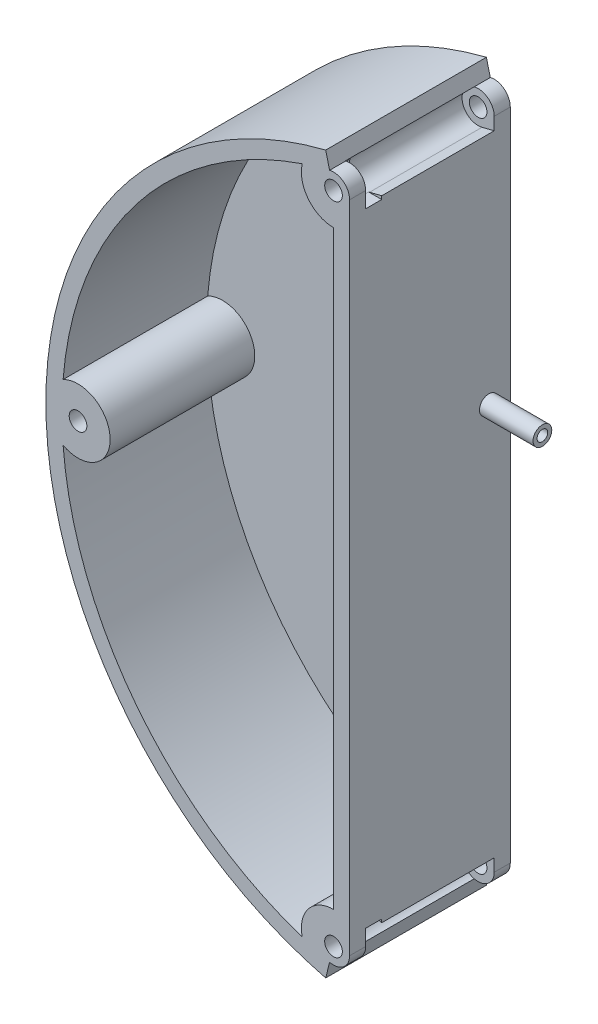
SolidWorks part; units mm, degrees
ref_plane "Front Plane" through (0, 0, 0) normal (0, 0, 1) x (1, 0, 0)
ref_plane "Top Plane" through (0, 0, 0) normal (0, 1, 0) x (1, 0, 0)
ref_plane "Right Plane" through (0, 0, 0) normal (1, 0, 0) x (0, 0, -1)
sketch "Sketch1" plane through (0, 0, 0) normal (0, 0, 1) x (1, 0, 0)
  line L0 (-12.3, -61.1139) -> (-12.3, 61.1139)
  line L1 (-12, -28.4) -> (-12, -52) construction
  line L2 (-16.7571, 66.9343) -> (-16.0286, 64.0241)
  line L4 (-16.7571, -66.9343) -> (-16.0286, -64.0241)
  line L5 (-63, 0) -> (0, 0) construction
  arc A1 (-16.0286, -64.0241) -> (-12.3, -61.1139) centre (-15.3, -61.1139) cw
  arc A3 (-16.0286, 64.0241) -> (-12.3, 61.1139) centre (-15.3, 61.1139) ccw
  circle A4 centre (-63, 0) radius 3
  arc A6 (-16.7571, 66.9343) -> (-16.7571, -66.9343) centre (0, 0) ccw
  dimension "D2" = 3
  dimension "D6" = 3
  dimension "D7" = 14.055
  dimension "D8" = 6
  dimension "D4" = 69
  dimension "D1" = 0.3
  dimension "D3" = 3
  dimension "D5" = 3
  dimension "D9" = 63
  dimension "D10" = 14.055
extrude "Boss-Extrude2" add sketch "Sketch1" along normal blind 30
shell "Shell1" thickness 3 removed face at (-24.7296, 0, 30)
sketch "Sketch3" plane through (-12.3, 0, 0) normal (1, 0, 0) x (0, 1, 0)
  line L0 (-61.1139, 0) -> (61.1139, 0) construction
  circle A0 centre (15, 4) radius 1.75
  dimension "D1" = 3.5
  dimension "D2" = 4
  dimension "D3" = 15
extrude "Boss-Extrude3" add sketch "Sketch3" along normal blind 10
sketch "Sketch5" plane through (0, 0, 0) normal (0, 0, 1) x (1, 0, 0)
  line L0 (-12.3, -61.1139) -> (-12.3, 61.1139)
  line L2 (-16.7571, 66.9343) -> (-16.0286, 64.0241)
  line L4 (-16.7571, -66.9343) -> (-16.0286, -64.0241)
  line L5 (-63, 0) -> (0, 0) construction
  circle A4 centre (-63, 0) radius 1.65
  circle A5 centre (-15.3, 61.1139) radius 1.65
  arc A6 (-16.7571, 66.9343) -> (-16.7571, -66.9343) centre (0, 0) ccw
  arc A7 (-16.0286, 64.0241) -> (-12.3, 61.1139) centre (-15.3, 61.1139) cw
  circle A8 centre (-15.3, -61.1139) radius 1.65
  arc A9 (-12.3, -61.1139) -> (-16.0286, -64.0241) centre (-15.3, -61.1139) cw
  dimension "D2" = 3.3
  dimension "D8" = 3.3
  dimension "D1" = 3.3
  dimension "D3" = 3
  dimension "D5" = 3
extrude "Boss-Extrude4" add sketch "Sketch5" along normal blind 3 contours A4 L0 A7 L2 A6 L4 A9 A8 A5 region at (-36.1775, 0, 0)
sketch "Sketch6" plane through (0, 0, 30) normal (0, 0, 1) x (1, 0, 0)
  line L0 (-63, 3) -> (-68.9348, 3)
  line L1 (-63, -3) -> (-68.9348, -3)
  line L2 (-16.0286, -64.0241) -> (-14.5714, -58.2037) construction
  line L3 (-14.5714, -58.2037) -> (-12.3, -58.7724)
  line L4 (-12.3, -61.1139) -> (-12.3, 61.1139) construction
  line L5 (-12.3, -58.7724) -> (-12.3, -61.1139)
  line L6 (-16.0286, 64.0241) -> (-14.5714, 58.2037) construction
  line L7 (-14.5714, 58.2037) -> (-12.3, 58.7724)
  line L8 (-12.3, 58.7724) -> (-12.3, 61.1139)
  arc A1 (-63, -3) -> (-63, 3) centre (-63, 0) ccw
  arc A2 (-12.3, -61.1139) -> (-14.5714, -58.2037) centre (-15.3, -61.1139) ccw
  arc A3 (-14.5714, 58.2037) -> (-12.3, 61.1139) centre (-15.3, 61.1139) ccw
  arc A4 (-16.7571, 66.9343) -> (-16.7571, -66.9343) centre (0, 0) ccw construction
  arc A5 (-68.9348, 3) -> (-68.9348, -3) centre (-68.9348, 0) ccw
  arc A6 (-12.3, -61.1139) -> (-16.0286, -64.0241) centre (-15.3, -61.1139) ccw construction
  arc A7 (-16.0286, 64.0241) -> (-12.3, 61.1139) centre (-15.3, 61.1139) ccw construction
extrude "Cut-Extrude1" cut sketch "Sketch6" against normal up to surface (27 mm away) up to face at (-61.35, 0, 3)
sketch "Sketch7" plane through (0, 0, 30) normal (0, 0, 1) x (1, 0, 0)
  line L0 (-13.5968, -58.1639) -> (-11.8936, -58.1639)
  line L1 (-11.8936, -61.1139) -> (-13.5968, -58.1639) construction
  line L2 (-13.5968, -58.1639) -> (-17.0032, -58.1639)
  line L3 (-17.0032, -58.1639) -> (-18.7064, -61.1139)
  line L4 (-18.7064, -61.1139) -> (-17.0032, -64.0639)
  line L5 (-17.0032, -64.0639) -> (-13.5968, -64.0639)
  line L6 (-13.5968, -64.0639) -> (-11.8936, -61.1139)
  line L7 (-11.8936, 61.1139) -> (-13.5968, 64.0639)
  line L8 (-13.5968, 64.0639) -> (-17.0032, 64.0639)
  line L9 (-17.0032, 64.0639) -> (-18.7064, 61.1139)
  line L10 (-18.7064, 61.1139) -> (-17.0032, 58.1639)
  line L11 (-17.0032, 58.1639) -> (-13.5968, 58.1639)
  line L12 (-13.5968, 58.1639) -> (-11.8936, 61.1139) construction
  line L13 (-59.5936, 0) -> (-61.2968, 2.95)
  line L14 (-61.2968, 2.95) -> (-64.7032, 2.95)
  line L15 (-64.7032, 2.95) -> (-66.4064, 0)
  line L16 (-66.4064, 0) -> (-64.7032, -2.95)
  line L17 (-64.7032, -2.95) -> (-61.2968, -2.95)
  line L18 (-61.2968, -2.95) -> (-59.5936, 0)
  line L19 (-11.8936, -58.1639) -> (-11.8936, -61.1139)
  line L20 (-13.5968, 58.1639) -> (-11.8936, 58.1639)
  line L21 (-11.8936, 58.1639) -> (-11.8936, 61.1139)
  circle A0 centre (-15.3, -61.1139) radius 2.95 construction
  circle A1 centre (-15.3, 61.1139) radius 2.95 construction
  circle A2 centre (-63, 0) radius 2.95 construction
  dimension "D1" = 5.9
  dimension "D2" = 5.9
  dimension "D3" = 5.9
extrude "Cut-Extrude2" cut sketch "Sketch7" against normal blind 3 from offset 3 offset against normal yes
sketch "Sketch8" plane through (0, 0, 30) normal (0, 0, 1) x (1, 0, 0)
  line L0 (-63, 3) -> (-68.9348, 3)
  line L1 (-68.9348, 3) -> (-68.9348, -3)
  line L2 (-68.9348, -3) -> (-63, -3) construction
  line L3 (-63, -3) -> (-68.9348, -3) construction
  line L4 (-68.9348, -3) -> (-63, -3)
  line L5 (-12.3, -58.7724) -> (-14.5714, -58.2037)
  line L6 (-12.3, -58.7724) -> (-12.3, -61.1139)
  line L7 (-12.3, 61.1139) -> (-12.3, 58.7724)
  line L8 (-14.5714, 58.2037) -> (-12.3, 58.7724)
  circle A0 centre (-63, 0) radius 1.65
  arc A1 (-63, -3) -> (-63, 3) centre (-63, 0) ccw
  circle A2 centre (-15.3, -61.1139) radius 1.65
  arc A3 (-14.5714, -58.2037) -> (-12.3, -61.1139) centre (-15.3, -61.1139) ccw
  circle A4 centre (-15.3, 61.1139) radius 1.65
  arc A5 (-12.3, 61.1139) -> (-14.5714, 58.2037) centre (-15.3, 61.1139) ccw
extrude "Boss-Extrude5" add sketch "Sketch8" against normal blind 3
sketch "Sketch9" plane through (-2.3, 0, 0) normal (1, 0, 0) x (0, 1, 0)
  circle A0 centre (15, 4) radius 1
  dimension "D1" = 2
extrude "Cut-Extrude3" cut sketch "Sketch9" against normal blind 30
